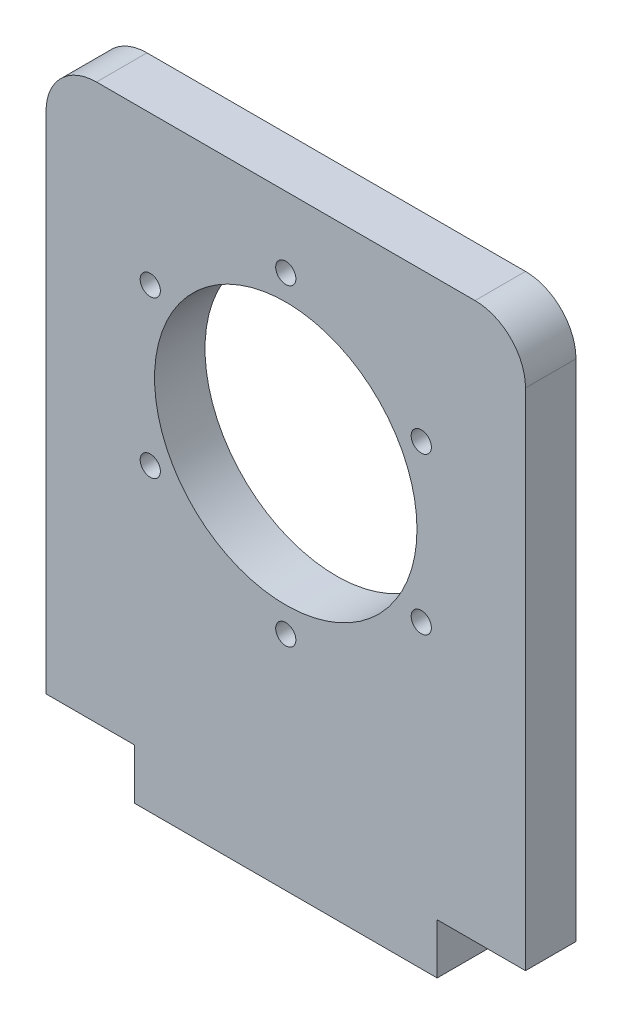
SolidWorks part; units mm, degrees
ref_plane "Front Plane" through (0, 0, 0) normal (0, 0, 1) x (1, 0, 0)
ref_plane "Top Plane" through (0, 0, 0) normal (0, 1, 0) x (1, 0, 0)
ref_plane "Right Plane" through (0, 0, 0) normal (1, 0, 0) x (0, 0, -1)
sketch "Sketch1" plane through (0, 0, 0) normal (0, 0, 1) x (1, 0, 0)
  line L0 (0, 45) -> (0, 0) construction
  line L5 (-47.5, 45) -> (47.5, 45)
  line L6 (-47.5, 45) -> (-47.5, -65)
  line L7 (-47.5, -65) -> (47.5, -65)
  line L8 (47.5, 45) -> (47.5, -65)
  line L9 (30, -65) -> (-30, -65)
  line L10 (30, -65) -> (30, -75)
  line L11 (-30, -65) -> (-30, -75)
  line L12 (30, -75) -> (-30, -75)
  circle A5 centre (0, 0) radius 26
  circle A6 centre (0, 0) radius 31 construction
  circle A7 centre (0, 31) radius 2
  circle A8 centre (26.8468, 15.5) radius 2
  circle A9 centre (26.8468, -15.5) radius 2
  circle A10 centre (0, -31) radius 2
  circle A11 centre (-26.8468, -15.5) radius 2
  circle A12 centre (-26.8468, 15.5) radius 2
  point P0 (0, 0)
  point P11 (0, -65)
  point P12 (0, -65)
  dimension "D1" = 95
  dimension "D4" = 62
  dimension "D6" = 6
  dimension "D3" = 52
  dimension "D5" = 4
  dimension "D2" = 110
  dimension "D7" = 45
  dimension "D8" = 60
  dimension "D9" = 10
extrude "Boss-Extrude1" add sketch "Sketch1" along normal blind 10 contours L8 L5 L6 L7 A12 A11 A10 A9 A8 A7 A5 | L12 L10 L7 L11 region at (0, 43.5466, 0) region at (0, -70, 0)
fillet "Fillet1" radius 10 2 edges at (47.5, 45, 5) (-47.5, 45, 5)
